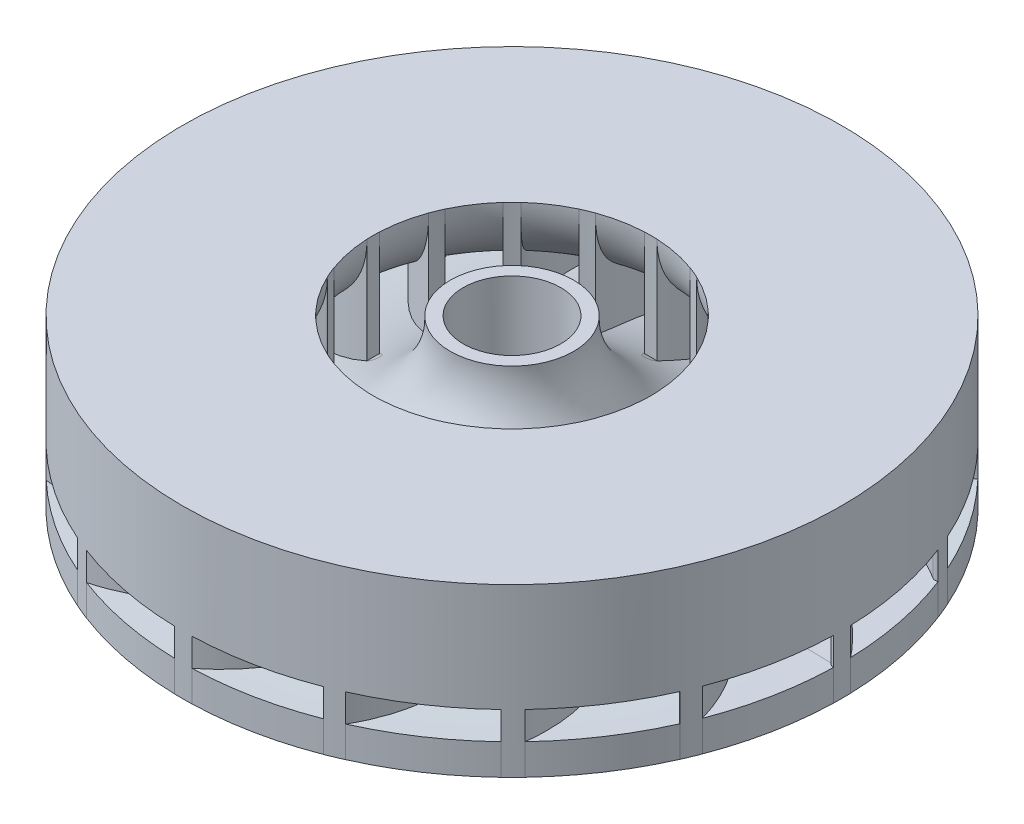
SolidWorks part; units mm, degrees
other "Markup1"
sketch "Sketch14" plane through (34.9924, 18.1689, 34.9924) normal (0.4024, 0.9092, 0.107) x (-0.9091, 0.4106, -0.0699)
material "AA356.0-F"
ref_plane "Front Plane" through (0, 0, 0) normal (0, 0, 1) x (1, 0, 0)
ref_plane "Top Plane" through (0, 0, 0) normal (0, 1, 0) x (1, 0, 0)
ref_plane "Right Plane" through (0, 0, 0) normal (1, 0, 0) x (0, 0, -1)
curve "Shroud Curve"
curve "Impeller Curve"
curve "Blade Curve"
sketch "Sketch2" plane through (0, 0, 0) normal (0, 0, 1) x (1, 0, 0)
  line L0 (14.2896, 17.1821) -> (33.9139, 17.1821)
  line L1 (33.9139, 17.1821) -> (33.9139, 6.0439)
  spline S0 degree 3 poles (-985.6672, 25.6238) (17.121, 24.6036) (14.2699, 20.8626) (14.29, 17.0771) (14.2924, 16.9214) (14.3025, 16.6646) (14.3304, 16.2921) (14.3832, 15.869) (14.4663, 15.4189) (14.5673, 15.0013) (14.692, 14.5874) (14.8412, 14.1777) (15.0158, 13.7731) (15.2158, 13.374) (15.4419, 12.981) (15.6996, 12.5875) (15.9902, 12.1947) (16.3155, 11.8043) (16.6762, 11.4178) (17.0667, 11.0427) (17.4864, 10.6798) (17.9347, 10.329) (18.4109, 9.9911) (18.9142, 9.6665) (19.4435, 9.3553) (20.0062, 9.0533) (20.6105, 8.7577) (21.2468, 8.4745) (21.9134, 8.2045) (22.6083, 7.9485) (23.3475, 7.7013) (24.1283, 7.4655) (24.9558, 7.241) (25.8242, 7.0305) (26.7261, 6.8369) (27.6431, 6.6639) (28.555, 6.5139) (29.435, 6.3888) (30.2578, 6.2886) (30.995, 6.2121) (31.6335, 6.1561) (32.1708, 6.1163) (32.6141, 6.0889) (32.9737, 6.0705) (33.2588, 6.0586) (33.476, 6.0514) (33.6399, 6.0473) (33.7596, 6.0451) (33.8432, 6.0441) (33.8894, 6.0439) (35.7046, 6.0419) (37.504, 6.9456) (38.7227, -993.9019) knots -0.448256 -0.448256 -0.448256 -0.448256 0.001273 0.002543 0.008858 0.020084 0.03357 0.053959 0.071547 0.088816 0.10582 0.123722 0.141437 0.159019 0.177608 0.196155 0.215799 0.236589 0.257482 0.279621 0.301942 0.324462 0.348334 0.372436 0.39676 0.422462 0.44954 0.477978 0.506547 0.536376 0.567388 0.600661 0.634851 0.670917 0.708547 0.746233 0.783584 0.820144 0.853551 0.883668 0.909634 0.93095 0.948727 0.963266 0.974429 0.983176 0.989512 0.994228 0.997631 0.999605 0.999804 1.216827 1.216827 1.216827 1.216827 only from (14.2896, 17.1821) to (33.9139, 6.0439) construction
  spline S1 degree 3 poles (14.2896, 17.1821) (14.2896, 17.1715) (14.2896, 17.1505) (14.29, 17.0771) (14.2924, 16.9214) (14.3025, 16.6646) (14.3304, 16.2921) (14.3832, 15.869) (14.4663, 15.4189) (14.5673, 15.0013) (14.692, 14.5874) (14.8412, 14.1777) (15.0158, 13.7731) (15.2158, 13.374) (15.4419, 12.981) (15.6996, 12.5875) (15.9902, 12.1947) (16.3155, 11.8043) (16.6762, 11.4178) (17.0667, 11.0427) (17.4864, 10.6798) (17.9347, 10.329) (18.4109, 9.9911) (18.9142, 9.6665) (19.4435, 9.3553) (20.0062, 9.0533) (20.6105, 8.7577) (21.2468, 8.4745) (21.9134, 8.2045) (22.6083, 7.9485) (23.3475, 7.7013) (24.1283, 7.4655) (24.9558, 7.241) (25.8242, 7.0305) (26.7261, 6.8369) (27.6431, 6.6639) (28.555, 6.5139) (29.435, 6.3888) (30.2578, 6.2886) (30.995, 6.2121) (31.6335, 6.1561) (32.1708, 6.1163) (32.6141, 6.0889) (32.9737, 6.0705) (33.2588, 6.0586) (33.476, 6.0514) (33.6399, 6.0473) (33.7596, 6.0451) (33.8432, 6.0441) (33.8894, 6.0439) (33.909, 6.0439) (33.9123, 6.0439) (33.9139, 6.0439) knots 0 0 0 0 0.001273 0.002543 0.008858 0.020084 0.03357 0.053959 0.071547 0.088816 0.10582 0.123722 0.141437 0.159019 0.177608 0.196155 0.215799 0.236589 0.257482 0.279621 0.301942 0.324462 0.348334 0.372436 0.39676 0.422462 0.44954 0.477978 0.506547 0.536376 0.567388 0.600661 0.634851 0.670917 0.708547 0.746233 0.783584 0.820144 0.853551 0.883668 0.909634 0.93095 0.948727 0.963266 0.974429 0.983176 0.989512 0.994228 0.997631 0.999605 0.999804 1 1 1 1
ref_axis "Axis1" through (0, 16.8793, 0) along (0, -1, 0)
revolve "Shroud" add sketch "Sketch2" angle 360 about axis through (0, 16.8793, 0) along (0, -1, 0)
sketch "Sketch3" plane through (0, 0, 0) normal (0, 0, 1) x (1, 0, 0)
  line L0 (33.9128, 3.175) -> (33.9128, 0)
  line L1 (33.9128, 0) -> (0, 0)
  line L2 (0, 0) -> (0, 17.1821)
  line L3 (33.9139, 17.1821) -> (-33.9139, 17.1821) construction
  line L4 (6.35, 17.1685) -> (0, 17.1821)
  spline S7 degree 3 poles (-1991.3665, 109.7009) (15.6852, 23.4896) (6.4344, 20.476) (6.3459, 17.0645) (6.3444, 17.0058) (6.3434, 16.947) (6.3404, 16.6729) (6.3533, 16.2816) (6.4048, 15.7563) (6.4711, 15.3126) (6.5686, 14.836) (6.6969, 14.3482) (6.8639, 13.8337) (7.066, 13.3147) (7.3118, 12.7771) (7.594, 12.2427) (7.9215, 11.699) (8.2837, 11.1664) (8.6895, 10.6336) (9.137, 10.1057) (9.6369, 9.5753) (10.1877, 9.0493) (10.7869, 8.5341) (11.4314, 8.0351) (12.1178, 7.5568) (12.8306, 7.1101) (13.5662, 6.695) (14.3337, 6.3043) (15.1445, 5.9339) (15.9967, 5.5857) (16.8758, 5.2653) (17.7806, 4.9716) (18.7099, 4.7037) (19.6624, 4.4606) (20.6367, 4.2412) (21.6306, 4.0447) (22.6521, 3.8684) (23.7077, 3.711) (24.8016, 3.5721) (25.9239, 3.4532) (27.0714, 3.3541) (28.244, 3.275) (29.4928, 3.2133) (30.6331, 3.1786) (31.5843, 3.1645) (32.226, 3.1616) (32.6964, 3.1629) (33.0402, 3.1656) (33.303, 3.1684) (33.5124, 3.1709) (33.6836, 3.173) (33.8026, 3.1742) (33.8663, 3.1747) (33.8858, 3.1748) (33.8929, 3.1749) (33.8999, 3.1749) (35.0826, 3.1853) (36.2737, -0.1737) (31.0149, 2002.8901) knots -0.294083 -0.294083 -0.294083 -0.294083 0.001321 0.003038 0.004754 0.006471 0.008186 0.028756 0.040733 0.054397 0.068031 0.083322 0.098551 0.115379 0.132085 0.150292 0.168289 0.187646 0.206684 0.226919 0.24823 0.270495 0.293593 0.317412 0.341854 0.366841 0.391061 0.415809 0.442244 0.46911 0.496416 0.524176 0.552404 0.581103 0.610263 0.639854 0.669822 0.701044 0.733318 0.766378 0.799876 0.834181 0.869306 0.90937 0.934086 0.952614 0.965565 0.975289 0.982722 0.988577 0.993635 0.99771 0.999002 0.999211 0.999418 0.999624 0.999828 1.102994 1.102994 1.102994 1.102994 only from (6.35, 17.1685) to (33.9128, 3.175) construction
  spline S8 degree 3 poles (6.35, 17.1685) (6.3492, 17.1535) (6.3474, 17.1188) (6.3459, 17.0645) (6.3444, 17.0058) (6.3434, 16.947) (6.3404, 16.6729) (6.3533, 16.2816) (6.4048, 15.7563) (6.4711, 15.3126) (6.5686, 14.836) (6.6969, 14.3482) (6.8639, 13.8337) (7.066, 13.3147) (7.3118, 12.7771) (7.594, 12.2427) (7.9215, 11.699) (8.2837, 11.1664) (8.6895, 10.6336) (9.137, 10.1057) (9.6369, 9.5753) (10.1877, 9.0493) (10.7869, 8.5341) (11.4314, 8.0351) (12.1178, 7.5568) (12.8306, 7.1101) (13.5662, 6.695) (14.3337, 6.3043) (15.1445, 5.9339) (15.9967, 5.5857) (16.8758, 5.2653) (17.7806, 4.9716) (18.7099, 4.7037) (19.6624, 4.4606) (20.6367, 4.2412) (21.6306, 4.0447) (22.6521, 3.8684) (23.7077, 3.711) (24.8016, 3.5721) (25.9239, 3.4532) (27.0714, 3.3541) (28.244, 3.275) (29.4928, 3.2133) (30.6331, 3.1786) (31.5843, 3.1645) (32.226, 3.1616) (32.6964, 3.1629) (33.0402, 3.1656) (33.303, 3.1684) (33.5124, 3.1709) (33.6836, 3.173) (33.8026, 3.1742) (33.8663, 3.1747) (33.8858, 3.1748) (33.8929, 3.1749) (33.8999, 3.1749) (33.9066, 3.175) (33.9109, 3.175) (33.9128, 3.175) knots 0 0 0 0 0.001321 0.003038 0.004754 0.006471 0.008186 0.028756 0.040733 0.054397 0.068031 0.083322 0.098551 0.115379 0.132085 0.150292 0.168289 0.187646 0.206684 0.226919 0.24823 0.270495 0.293593 0.317412 0.341854 0.366841 0.391061 0.415809 0.442244 0.46911 0.496416 0.524176 0.552404 0.581103 0.610263 0.639854 0.669822 0.701044 0.733318 0.766378 0.799876 0.834181 0.869306 0.90937 0.934086 0.952614 0.965565 0.975289 0.982722 0.988577 0.993635 0.99771 0.999002 0.999211 0.999418 0.999624 0.999828 1 1 1 1
revolve "Impeller" add sketch "Sketch3" angle 360 about axis through (0, 16.8793, 0) along (0, -1, 0)
sketch "Sketch6" plane through (0, 0, 0) normal (0, 1, 0) x (1, 0, 0)
  arc A1 (14.2692, -0.6474) -> (14.31, 0.6474) centre (14.2896, 0) cw
  arc A2 (30.638, -13.2667) -> (31.9028, -12.987) centre (31.2704, -13.1269) ccw
  arc A4 (31.013, -13.7212) -> (31.6811, -12.0991) centre (0, 0) ccw
  circle A6 centre (0, 0) radius 33.9128 construction
  arc A9 (15.0709, 0.613) -> (15.0678, -0.6846) centre (0, 0) cw
  circle A12 centre (0, 0) radius 14.2896 construction
  circle A13 centre (0, 0) radius 14.2896 construction
  spline S0 degree 3 poles (29.1527, 999.8802) (2.6027, -2.0333) (8.5201, 0.1935) (14.47, -0.006) (14.7444, -0.017) (15.2838, -0.047) (16.0195, -0.1066) (16.8994, -0.2107) (17.8059, -0.3553) (18.6971, -0.537) (19.5715, -0.7574) (20.405, -1.0093) (21.1987, -1.2906) (21.9628, -1.6029) (22.697, -1.9455) (23.401, -2.3173) (24.074, -2.7162) (24.7234, -3.1458) (25.3546, -3.6107) (25.9646, -4.11) (26.5566, -4.6475) (27.132, -5.2274) (27.7008, -5.8649) (28.2624, -6.5684) (28.8239, -7.3613) (29.3515, -8.2108) (29.8101, -9.0583) (30.1771, -9.8308) (30.4638, -10.5106) (30.6902, -11.1112) (30.8707, -11.644) (31.0313, -12.1706) (31.1418, -12.5811) (31.2149, -12.8827) (31.2453, -13.0144) (31.2619, -13.0887) (31.2681, -13.1165) (31.8566, -15.7731) (31.8137, -18.5676) (1009.2473, 194.9709) knots -0.749934 -0.749934 -0.749934 -0.749934 0.001801 0.003598 0.017879 0.037227 0.073264 0.113069 0.151484 0.191631 0.230352 0.267746 0.303909 0.33893 0.374178 0.408369 0.44158 0.475057 0.508762 0.542655 0.576689 0.611857 0.647988 0.686837 0.727913 0.773243 0.815755 0.852134 0.88353 0.910883 0.93491 0.95607 0.981881 0.989727 0.996094 0.999315 0.999546 0.999774 1.350254 1.350254 1.350254 1.350254 only from (14.2896, 0) to (31.2704, -13.1269) construction
  spline S1 degree 3 poles (14.2896, 0) (14.3035, -0.0004) (14.3453, -0.0018) (14.4701, -0.006) (14.7311, -0.0166) (15.2304, -0.0435) (15.9421, -0.0994) (16.7994, -0.1973) (17.6976, -0.3359) (18.5936, -0.5137) (19.4727, -0.7304) (20.3109, -0.9787) (21.1092, -1.2567) (21.8777, -1.5659) (22.6164, -1.9056) (23.3247, -2.2748) (24.002, -2.6713) (24.6557, -3.0988) (25.2912, -3.5617) (25.9055, -4.0592) (26.5018, -4.5953) (27.0817, -5.1741) (27.65, -5.8051) (28.2122, -6.5022) (28.7719, -7.2835) (29.3068, -8.1341) (29.7723, -8.9839) (30.148, -9.7661) (30.4395, -10.45) (30.6702, -11.0555) (30.8545, -11.5937) (31.0233, -12.1415) (31.1389, -12.5689) (31.2155, -12.8854) (31.2453, -13.0144) (31.2627, -13.0921) (31.2692, -13.1217) (31.2704, -13.1269) knots 0 0 0 0 0.001801 0.005393 0.016104 0.035482 0.069882 0.108171 0.146755 0.187074 0.225954 0.263496 0.299797 0.334945 0.370316 0.40462 0.437936 0.471515 0.505319 0.539308 0.573438 0.608704 0.644938 0.682922 0.724171 0.768833 0.812464 0.849081 0.880722 0.908332 0.932632 0.95409 0.982247 0.989727 0.996094 0.999315 1 1 1 1
  spline S2 degree 1 poles (14.2692, -0.6474) (30.638, -13.2667) knots 0 0 1 1 construction
  spline S3 degree 3 poles (14.2692, -0.6474) (14.4674, -0.6536) (14.8024, -0.6677) (16.6862, -0.7857) (20.2272, -1.376) (25.0147, -3.7201) (28.795, -7.9373) (30.237, -11.4541) (30.638, -13.2667) knots 0 0 0 0 0.026426 0.044044 0.25 0.5 0.75 1 1 1 1
  spline S4 degree 1 poles (14.31, 0.6474) (31.9028, -12.987) knots 0 0 1 1 construction
  spline S5 degree 3 poles (14.31, 0.6474) (14.5007, 0.6414) (14.8171, 0.6283) (16.8017, 0.5101) (20.5738, -0.1052) (25.8167, -2.6593) (29.6637, -6.9585) (31.2206, -10.4525) (31.7637, -12.3924) (31.8537, -12.7652) (31.9028, -12.987) knots 0 0 0 0 0.023975 0.039958 0.25 0.5 0.75 0.952724 0.971634 1 1 1 1
  dimension "D3" = 0.7937
  dimension "D1" = 0.6477
sketch "Sketch5" plane through (0, 0, 0) normal (0, -1, 0) x (1, 0, 0)
  circle A0 centre (0, 0) radius 5.0215
  dimension "D1" = 10.043
extrude "Shaft Hole" cut sketch "Sketch5" against normal through all
extrude "Blade" add sketch "Sketch6" along normal through all contours S5 A1 A9 S1 A4 | A9 S3 A2 A4 S1 | S3 A2 S5 A1 region at (15.291, 0, 0.3658) region at (25.4108, 0, 3.1183)
pattern_circular "Other Blades" count 16 over 360 about axis through (0, 16.8793, 0) along (0, -1, 0) of "Blade"
sketch "Sketch11" plane through (0, 0, 0) normal (0, 0, 1) x (1, 0, 0)
  line L0 (12.2275, 17.1821) -> (0.9443, 17.1821) construction
  line L5 (-33.9128, 0) -> (33.9128, 0) construction
  line L6 (33.9139, 17.1821) -> (-33.9139, 17.1821) construction
  line L7 (0, 0) -> (0, 17.1821) construction
  line L10 (14.2896, 17.1821) -> (14.2896, 6.3325)
  line L11 (14.2896, 17.1821) -> (6.3507, 17.1821)
  line L12 (14.2896, 17.1821) -> (14.2896, 20.3571)
  line L13 (14.2896, 20.3571) -> (6.3507, 20.3571)
  line L14 (6.3507, 20.3571) -> (6.3507, 17.1821)
  line L17 (-33.9139, 17.1821) -> (-40.2639, 17.1821)
  line L18 (-33.9139, 17.1821) -> (-33.9139, 0)
  line L19 (-33.9139, 0) -> (-40.2639, 0)
  line L20 (-40.2639, 17.1821) -> (-40.2639, 0)
  spline S0 degree 3 poles (-1985.5723, 25.8235) (18.7865, 26.5378) (14.2647, 21.8275) (14.29, 17.0771) (14.2924, 16.9214) (14.3025, 16.6646) (14.3304, 16.2921) (14.3832, 15.869) (14.4663, 15.4189) (14.5673, 15.0013) (14.692, 14.5874) (14.8412, 14.1777) (15.0158, 13.7731) (15.2158, 13.374) (15.4419, 12.981) (15.6996, 12.5875) (15.9902, 12.1947) (16.3155, 11.8043) (16.6762, 11.4178) (17.0667, 11.0427) (17.4864, 10.6798) (17.9347, 10.329) (18.4109, 9.9911) (18.9142, 9.6665) (19.4435, 9.3553) (20.0062, 9.0533) (20.6105, 8.7577) (21.2468, 8.4745) (21.9134, 8.2045) (22.6083, 7.9485) (23.3475, 7.7013) (24.1283, 7.4655) (24.9558, 7.241) (25.8242, 7.0305) (26.7261, 6.8369) (27.6431, 6.6639) (28.555, 6.5139) (29.435, 6.3888) (30.2578, 6.2886) (30.995, 6.2121) (31.6335, 6.1561) (32.1708, 6.1163) (32.6141, 6.0889) (32.9737, 6.0705) (33.2588, 6.0586) (33.476, 6.0514) (33.6399, 6.0473) (33.7596, 6.0451) (33.8432, 6.0441) (33.8894, 6.0439) (36.1713, 6.0413) (38.4378, 7.4755) (39.5447, -1993.8855) knots -0.564763 -0.564763 -0.564763 -0.564763 0.001273 0.002543 0.008858 0.020084 0.03357 0.053959 0.071547 0.088816 0.10582 0.123722 0.141437 0.159019 0.177608 0.196155 0.215799 0.236589 0.257482 0.279621 0.301942 0.324462 0.348334 0.372436 0.39676 0.422462 0.44954 0.477978 0.506547 0.536376 0.567388 0.600661 0.634851 0.670917 0.708547 0.746233 0.783584 0.820144 0.853551 0.883668 0.909634 0.93095 0.948727 0.963266 0.974429 0.983176 0.989512 0.994228 0.997631 0.999605 0.999804 1.273187 1.273187 1.273187 1.273187 only from (14.2896, 17.1821) to (33.9139, 6.0439) construction
  spline S1 degree 3 poles (-1991.3665, 109.7009) (15.6852, 23.4896) (6.4344, 20.476) (6.3459, 17.0645) (6.3444, 17.0058) (6.3434, 16.947) (6.3404, 16.6729) (6.3533, 16.2816) (6.4048, 15.7563) (6.4711, 15.3126) (6.5686, 14.836) (6.6969, 14.3482) (6.8639, 13.8337) (7.066, 13.3147) (7.3118, 12.7771) (7.594, 12.2427) (7.9215, 11.699) (8.2837, 11.1664) (8.6895, 10.6336) (9.137, 10.1057) (9.6369, 9.5753) (10.1877, 9.0493) (10.7869, 8.5341) (11.4314, 8.0351) (12.1178, 7.5568) (12.8306, 7.1101) (13.5662, 6.695) (14.3337, 6.3043) (15.1445, 5.9339) (15.9967, 5.5857) (16.8758, 5.2653) (17.7806, 4.9716) (18.7099, 4.7037) (19.6624, 4.4606) (20.6367, 4.2412) (21.6306, 4.0447) (22.6521, 3.8684) (23.7077, 3.711) (24.8016, 3.5721) (25.9239, 3.4532) (27.0714, 3.3541) (28.244, 3.275) (29.4928, 3.2133) (30.6331, 3.1786) (31.5843, 3.1645) (32.226, 3.1616) (32.6964, 3.1629) (33.0402, 3.1656) (33.303, 3.1684) (33.5124, 3.1709) (33.6836, 3.173) (33.8026, 3.1742) (33.8663, 3.1747) (33.8858, 3.1748) (33.8929, 3.1749) (33.8999, 3.1749) (35.0826, 3.1853) (36.2737, -0.1737) (31.0149, 2002.8901) knots -0.294083 -0.294083 -0.294083 -0.294083 0.001321 0.003038 0.004754 0.006471 0.008186 0.028756 0.040733 0.054397 0.068031 0.083322 0.098551 0.115379 0.132085 0.150292 0.168289 0.187646 0.206684 0.226919 0.24823 0.270495 0.293593 0.317412 0.341854 0.366841 0.391061 0.415809 0.442244 0.46911 0.496416 0.524176 0.552404 0.581103 0.610263 0.639854 0.669822 0.701044 0.733318 0.766378 0.799876 0.834181 0.869306 0.90937 0.934086 0.952614 0.965565 0.975289 0.982722 0.988577 0.993635 0.99771 0.999002 0.999211 0.999418 0.999624 0.999828 1.102994 1.102994 1.102994 1.102994 only from (6.35, 17.1685) to (33.9128, 3.175) construction
  spline S2 degree 3 poles (14.2896, 17.1821) (14.2896, 17.1715) (14.2896, 17.1505) (14.29, 17.0771) (14.2924, 16.9214) (14.3025, 16.6646) (14.3304, 16.2921) (14.3832, 15.869) (14.4663, 15.4189) (14.5673, 15.0013) (14.692, 14.5874) (14.8412, 14.1777) (15.0158, 13.7731) (15.2158, 13.374) (15.4419, 12.981) (15.6996, 12.5875) (15.9902, 12.1947) (16.3155, 11.8043) (16.6762, 11.4178) (17.0667, 11.0427) (17.4864, 10.6798) (17.9347, 10.329) (18.4109, 9.9911) (18.9142, 9.6665) (19.4435, 9.3553) (20.0062, 9.0533) (20.6105, 8.7577) (21.2468, 8.4745) (21.9134, 8.2045) (22.6083, 7.9485) (23.3475, 7.7013) (24.1283, 7.4655) (24.9558, 7.241) (25.8242, 7.0305) (26.7261, 6.8369) (27.6431, 6.6639) (28.555, 6.5139) (29.435, 6.3888) (30.2578, 6.2886) (30.995, 6.2121) (31.6335, 6.1561) (32.1708, 6.1163) (32.6141, 6.0889) (32.9737, 6.0705) (33.2588, 6.0586) (33.476, 6.0514) (33.6399, 6.0473) (33.7596, 6.0451) (33.8432, 6.0441) (33.8894, 6.0439) (33.909, 6.0439) (33.9123, 6.0439) (33.9139, 6.0439) knots 0 0 0 0 0.001273 0.002543 0.008858 0.020084 0.03357 0.053959 0.071547 0.088816 0.10582 0.123722 0.141437 0.159019 0.177608 0.196155 0.215799 0.236589 0.257482 0.279621 0.301942 0.324462 0.348334 0.372436 0.39676 0.422462 0.44954 0.477978 0.506547 0.536376 0.567388 0.600661 0.634851 0.670917 0.708547 0.746233 0.783584 0.820144 0.853551 0.883668 0.909634 0.93095 0.948727 0.963266 0.974429 0.983176 0.989512 0.994228 0.997631 0.999605 0.999804 1 1 1 1
  spline S3 degree 3 poles (6.3507, 17.1821) (6.3497, 17.1625) (6.3475, 17.1233) (6.3459, 17.0645) (6.3444, 17.0058) (6.3434, 16.947) (6.3404, 16.6729) (6.3533, 16.2816) (6.4048, 15.7563) (6.4711, 15.3126) (6.5686, 14.836) (6.6969, 14.3482) (6.8639, 13.8337) (7.066, 13.3147) (7.3118, 12.7771) (7.594, 12.2427) (7.9215, 11.699) (8.2837, 11.1664) (8.6895, 10.6336) (9.137, 10.1057) (9.6369, 9.5753) (10.1877, 9.0493) (10.7869, 8.5341) (11.4314, 8.0351) (12.1178, 7.5568) (12.8306, 7.1101) (13.5662, 6.695) (14.3337, 6.3043) (15.1445, 5.9339) (15.9967, 5.5857) (16.8758, 5.2653) (17.7806, 4.9716) (18.7099, 4.7037) (19.6624, 4.4606) (20.6367, 4.2412) (21.6306, 4.0447) (22.6521, 3.8684) (23.7077, 3.711) (24.8016, 3.5721) (25.9239, 3.4532) (27.0714, 3.3541) (28.244, 3.275) (29.4928, 3.2133) (30.6331, 3.1786) (31.5843, 3.1645) (32.226, 3.1616) (32.6964, 3.1629) (33.0402, 3.1656) (33.303, 3.1684) (33.5124, 3.1709) (33.6836, 3.173) (33.8026, 3.1742) (33.8663, 3.1747) (33.8858, 3.1748) (33.8929, 3.1749) (33.8999, 3.1749) (33.9066, 3.175) (33.9109, 3.175) (33.9128, 3.175) knots -0.000397 -0.000397 -0.000397 -0.000397 0.001321 0.003038 0.004754 0.006471 0.008186 0.028756 0.040733 0.054397 0.068031 0.083322 0.098551 0.115379 0.132085 0.150292 0.168289 0.187646 0.206684 0.226919 0.24823 0.270495 0.293593 0.317412 0.341854 0.366841 0.391061 0.415809 0.442244 0.46911 0.496416 0.524176 0.552404 0.581103 0.610263 0.639854 0.669822 0.701044 0.733318 0.766378 0.799876 0.834181 0.869306 0.90937 0.934086 0.952614 0.965565 0.975289 0.982722 0.988577 0.993635 0.99771 0.999002 0.999211 0.999418 0.999624 0.999828 1 1 1 1
  dimension "D1" = 6.35
  dimension "D2" = 3.175
revolve "Trimming" cut sketch "Sketch11" angle 360 about L7 region at (11.0166, 12.9517, 0) region at (10.3202, 18.7696, 0) region at (-37.0889, 8.591, 0)
sketch "Sketch13" plane through (0, 0, 0) normal (0, -1, 0) x (1, 0, 0)
  line L0 (-3.7548, 1.52) -> (-6.1452, 1.52)
  line L5 (-6.45, 1.2152) -> (-6.45, -1.2152)
  line L6 (-6.1452, -1.52) -> (-3.7548, -1.52)
  line L7 (-3.45, -1.2152) -> (-3.45, 1.2152)
  line L8 (-6.45, 0) -> (-3.45, 0) construction
  line L9 (-5, 1.52) -> (-5, -1.52) construction
  arc A0 (-6.1452, 1.52) -> (-6.45, 1.2152) centre (-6.1452, 1.2152) ccw
  arc A2 (-6.45, -1.2152) -> (-6.1452, -1.52) centre (-6.1452, -1.2152) ccw
  arc A3 (-3.7548, -1.52) -> (-3.45, -1.2152) centre (-3.7548, -1.2152) ccw
  arc A4 (-3.45, 1.2152) -> (-3.7548, 1.52) centre (-3.7548, 1.2152) ccw
  dimension "D1" = 0.3048
  dimension "D2" = 3.04
  dimension "D3" = 5
  dimension "D4" = 1.45
  dimension "D5" = 3
extrude "Keyway" cut sketch "Sketch13" against normal blind 9
